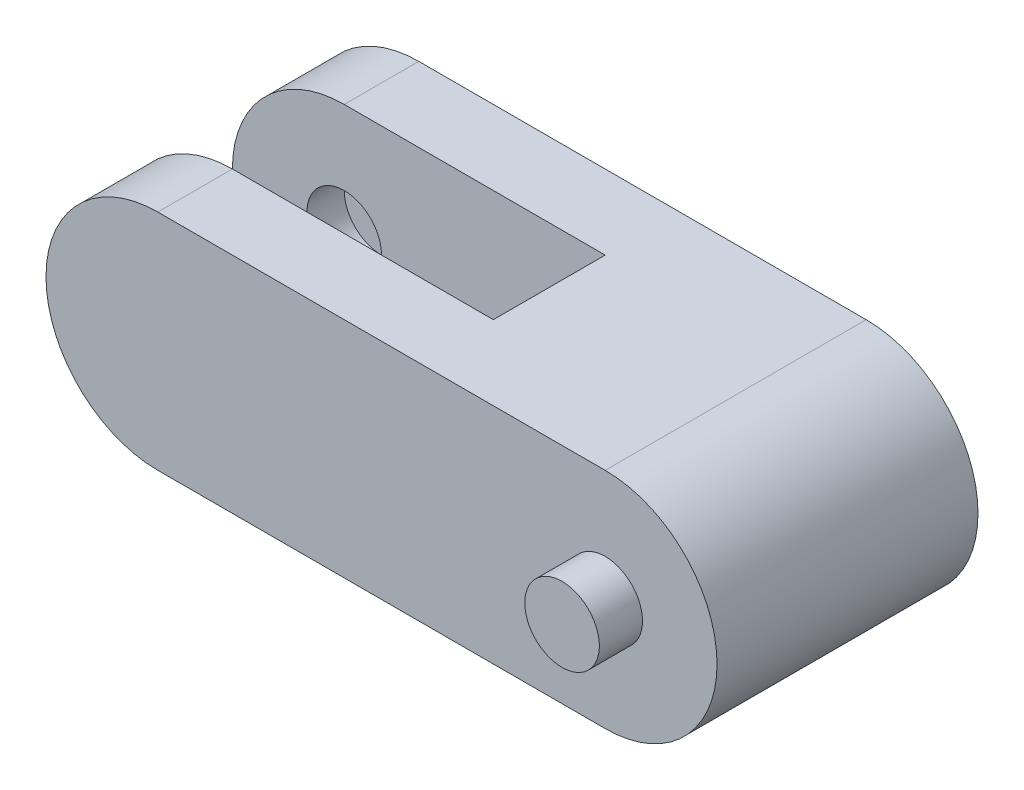
SolidWorks part; units mm, degrees
material "5052-H34"
ref_plane "Front Plane" through (0, 0, 0) normal (0, 0, 1) x (1, 0, 0)
ref_plane "Top Plane" through (0, 0, 0) normal (0, 1, 0) x (1, 0, 0)
ref_plane "Right Plane" through (0, 0, 0) normal (1, 0, 0) x (0, 0, -1)
sketch "Sketch2" plane through (0, 0, 0) normal (0, 0, 1) x (1, 0, 0)
  line L0 (-76.2, 38.1) -> (76.2, 38.1)
  line L2 (-76.2, -38.1) -> (76.2, -38.1)
  line L3 (0, 38.1) -> (0, -38.1) construction
  line L4 (-114.3, 0) -> (114.3, 0) construction
  arc A0 (76.2, 38.1) -> (76.2, -38.1) centre (76.2, 0) cw
  arc A1 (-76.2, 38.1) -> (-76.2, -38.1) centre (-76.2, 0) ccw
  point P10 (0, 0)
  dimension "D1" = 152.4
  dimension "D2" = 76.2
extrude "Boss-Extrude1" add sketch "Sketch2" along normal mid plane 88.9
sketch "Sketch3" plane through (0, 0, -44.45) normal (0, 0, -1) x (-1, 0, 0)
  circle A0 centre (-76.2, 0) radius 12.7
  dimension "D1" = 25.4
extrude "Boss-Extrude2" add sketch "Sketch3" along normal blind 14.7
mirror "Mirror1" about plane through (0, 0, 0) normal (0, 0, 1) of "Boss-Extrude2"
sketch "Sketch5" plane through (0, 0, 0) normal (0, 0, 1) x (1, 0, 0)
  line L0 (-76.2, 38.1) -> (12.7, 38.1)
  line L3 (76.2, 38.1) -> (-76.2, 38.1) construction
  line L4 (12.7, 38.1) -> (12.7, -38.1)
  line L5 (-76.2, -38.1) -> (76.2, -38.1) construction
  line L6 (12.7, -38.1) -> (-76.2, -38.1)
  arc A3 (-76.2, 38.1) -> (-76.2, -38.1) centre (-76.2, 0) ccw construction
  arc A4 (-76.2, 38.1) -> (-76.2, -38.1) centre (-76.2, 0) ccw
  dimension "D1" = 88.9
extrude "Cut-Extrude1" cut sketch "Sketch5" against normal mid plane 38.1
sketch "Sketch7" plane through (0, 0, -19.05) normal (0, 0, 1) x (1, 0, 0)
  circle A0 centre (-76.2, 0) radius 12.7
  dimension "D1" = 25.4
extrude "Cut-Extrude2" cut sketch "Sketch7" against normal blind 12.7
mirror "Mirror2" about plane through (0, 0, 0) normal (0, 0, 1) of "Cut-Extrude2"
